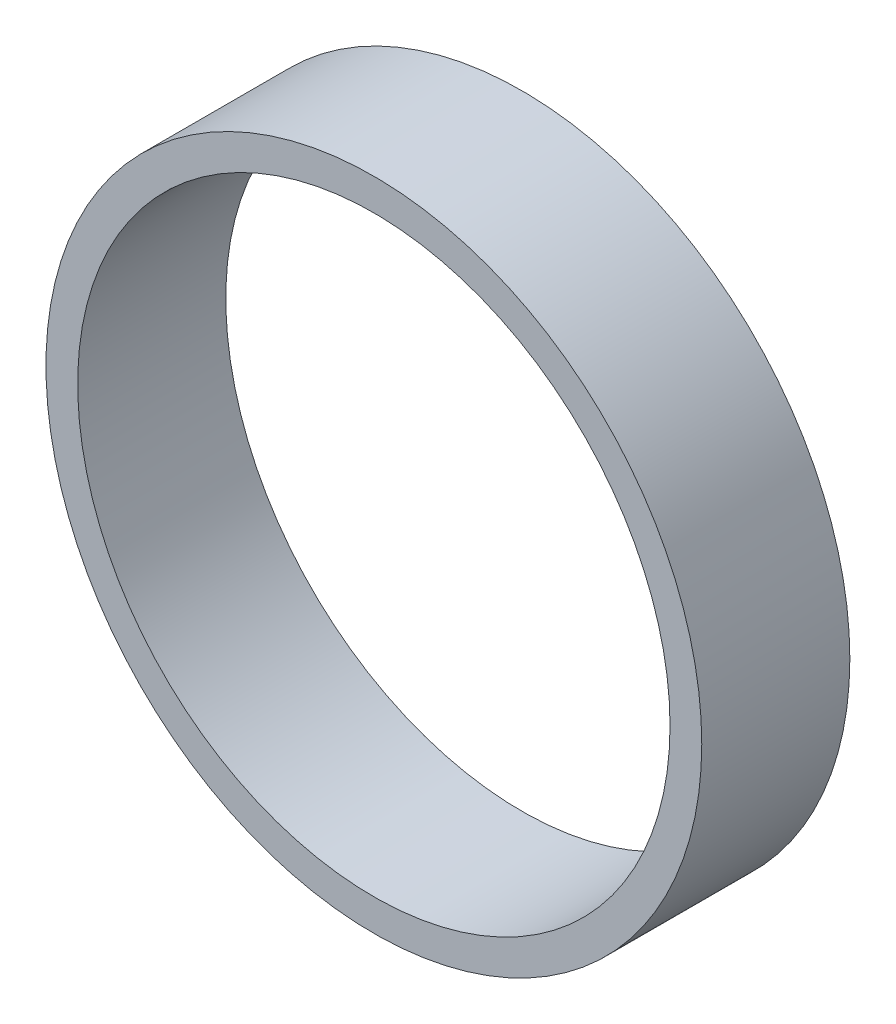
SolidWorks part; units mm, degrees
material "Leaded Commercial Bronze"
ref_plane "Front Plane" through (0, 0, 0) normal (0, 0, 1) x (1, 0, 0)
ref_plane "Top Plane" through (0, 0, 0) normal (0, 1, 0) x (1, 0, 0)
ref_plane "Right Plane" through (0, 0, 0) normal (1, 0, 0) x (0, 0, -1)
sketch "Sketch1" plane through (0, 0, 0) normal (0, 0, 1) x (1, 0, 0)
  circle A0 centre (0, 0) radius 49.2125
  circle A1 centre (0, 0) radius 44.45
  dimension "D1" = 98.425
  dimension "D2" = 88.9
extrude "Boss-Extrude1" add sketch "Sketch1" along normal mid plane 22.225
sketch "Sketch2" plane through (0, 0, 0) normal (0, 1, 0) x (1, 0, 0)
  circle A0 centre (0, 0) radius 1.5875
  dimension "D1" = 3.175
extrude "Cut-Extrude1" [suppressed] cut sketch "Sketch2" along normal through all
pattern_circular "CirPattern1" [suppressed] count 4 over 360 of bodies 102
